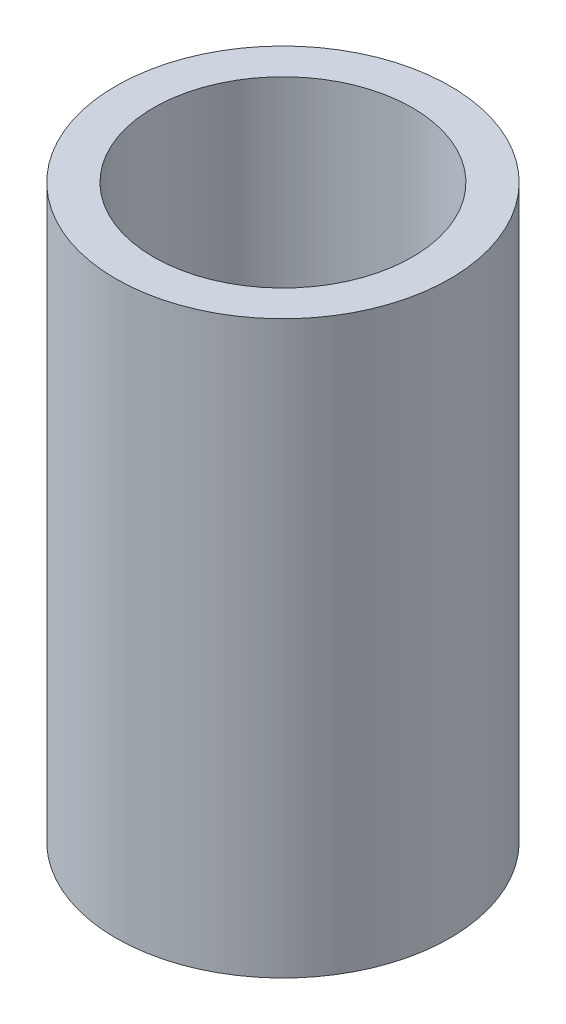
SolidWorks part; units mm, degrees
ref_plane "Front Plane" through (0, 0, 0) normal (0, 0, 1) x (1, 0, 0)
ref_plane "Top Plane" through (0, 0, 0) normal (0, 1, 0) x (1, 0, 0)
ref_plane "Right Plane" through (0, 0, 0) normal (1, 0, 0) x (0, 0, -1)
sketch "Sketch1" plane through (0, 0, 0) normal (0, 1, 0) x (1, 0, 0)
  circle A0 centre (0, 0) radius 17.5
  dimension "SLEEVE_OD" = 35
extrude "Boss-Extrude1" add sketch "Sketch1" along normal blind 59.8108
sketch "Sketch2" plane through (0, 0, 0) normal (0, 1, 0) x (1, 0, 0)
  circle A0 centre (0, 0) radius 13.5562
  dimension "BORE_D" = 27.1124
extrude "Cut-Extrude1" cut sketch "Sketch2" along normal through all
chamfer "Chamfer1" distance 3.0771 angle 52.104 rebuild error yes
